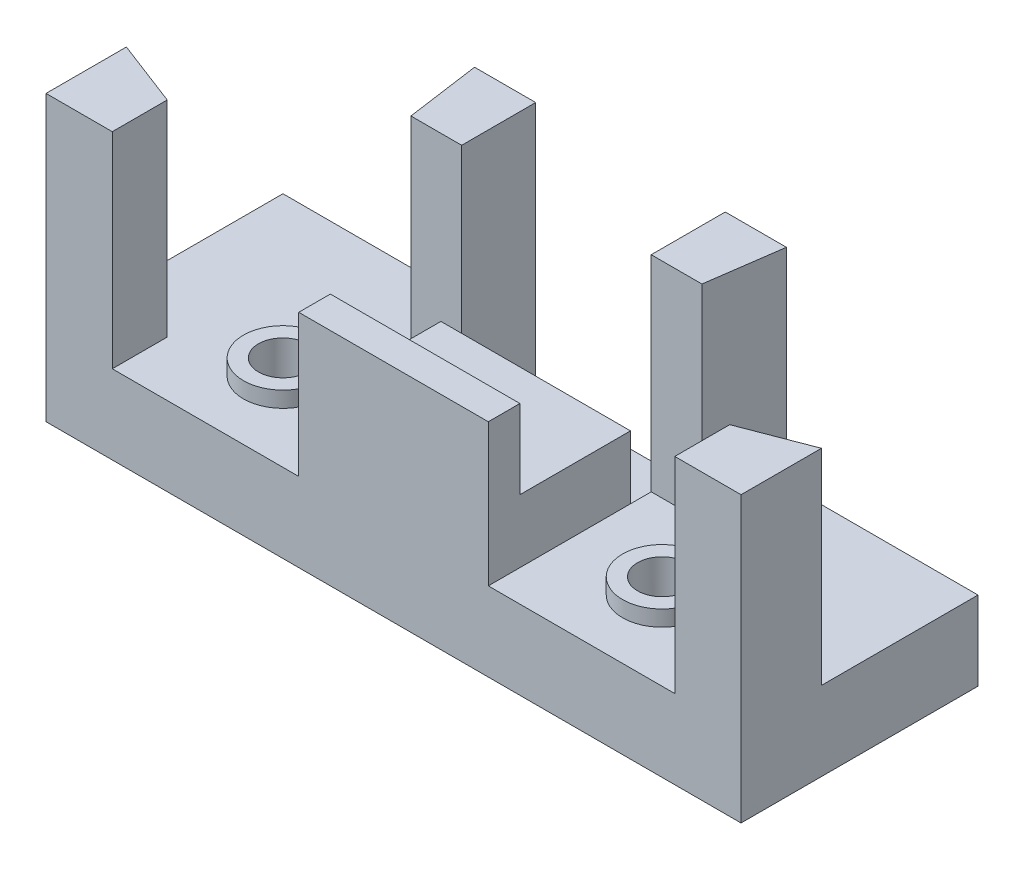
SolidWorks part; units mm, degrees
ref_plane "Front Plane" through (0, 0, 0) normal (0, 0, 1) x (1, 0, 0)
ref_plane "Top Plane" through (0, 0, 0) normal (0, 1, 0) x (1, 0, 0)
ref_plane "Right Plane" through (0, 0, 0) normal (1, 0, 0) x (0, 0, -1)
sketch "Sketch1" plane through (0, 0, 0) normal (0, 1, 0) x (1, 0, 0)
  line L1 (0, 0) -> (44, 0)
  line L2 (0, 0) -> (0, -15)
  line L3 (0, -15) -> (44, -15)
  line L4 (44, 0) -> (44, -15)
  dimension "D1" = 15
  dimension "D2" = 44
extrude "Boss-Extrude1" add sketch "Sketch1" along normal blind 5
sketch "Sketch2" plane through (0, 5, 0) normal (0, 1, 0) x (1, 0, 0)
  line L0 (44, 0) -> (0, 0) construction
  line L1 (16, 0) -> (28, 0)
  line L2 (16, 0) -> (16, -15)
  line L3 (16, -15) -> (28, -15)
  line L4 (28, 0) -> (28, -15)
  line L5 (0, -15) -> (44, -15) construction
  line L6 (22, 0) -> (22, -15) construction
  dimension "D1" = 6
  dimension "D2" = 6
extrude "Boss-Extrude2" add sketch "Sketch2" along normal blind 4
sketch "Sketch3" plane through (0, 5, 0) normal (0, 1, 0) x (1, 0, 0)
  line L0 (28, -15) -> (44, -15) construction
  line L4 (0, -15) -> (16, -15) construction
  line L5 (28, -15) -> (28, 0) construction
  line L6 (16, 0) -> (16, -15) construction
  circle A0 centre (10, -10) radius 1.55
  circle A1 centre (34, -10) radius 1.55
  dimension "D1" = 3.1
  dimension "D3" = 3.1
  dimension "D2" = 5
  dimension "D4" = 5
  dimension "D5" = 6
  dimension "D6" = 6
extrude "Cut-Extrude1" cut sketch "Sketch3" against normal blind 3
sketch "Sketch4" plane through (0, 9, 0) normal (0, 1, 0) x (1, 0, 0)
  line L1 (16, -15) -> (28, -15) construction
  line L2 (16, 0) -> (16, -15) construction
  circle A0 centre (22, -10) radius 1.55
  dimension "D1" = 3.1
  dimension "D2" = 5
  dimension "D3" = 6
extrude "Cut-Extrude2" cut sketch "Sketch4" against normal blind 3
sketch "Sketch5" plane through (0, 5, 0) normal (0, 1, 0) x (1, 0, 0)
  line L0 (22, 0) -> (22, -15) construction
  line L1 (28, 0) -> (16, 0) construction
  line L2 (16, -15) -> (28, -15) construction
  circle A0 centre (10, -10) radius 2.5
  circle A1 centre (10, -10) radius 1.55
  circle A2 centre (34, -10) radius 2.5
  circle A3 centre (34, -10) radius 1.55
  dimension "D1" = 5
extrude "Boss-Extrude3" add sketch "Sketch5" along normal blind 1
sketch "Sketch6" plane through (0, 9, 0) normal (0, 1, 0) x (1, 0, 0)
  line L0 (16, 0) -> (16, -15) construction
  line L1 (16, -13) -> (28, -13)
  line L2 (16, -13) -> (16, -15)
  line L3 (16, -15) -> (28, -15)
  line L4 (28, -13) -> (28, -15)
  dimension "D1" = 2
extrude "Boss-Extrude4" add sketch "Sketch6" along normal blind 5
sketch "Sketch8" plane through (0, 5, 0) normal (0, 1, 0) x (1, 0, 0)
  line L0 (34, -10) -> (44, -10) construction
  line L1 (44, -15) -> (44, 0) construction
  line L2 (34, -10) -> (44, -6.1614) construction
  line L3 (34, -10) -> (35.4054, 0) construction
  line L4 (44, 0) -> (28, 0) construction
  line L5 (34.7027, -5) -> (31.2368, -4.5129) construction
  line L6 (31.2368, -4.5129) -> (29.8332, -14.4994) construction
  line L7 (34, -10) -> (31.2123, -4.6869) construction
  line L8 (31.2123, -4.6869) -> (31.871, 0)
  line L11 (39, -8.0807) -> (40.2543, -11.3482) construction
  line L12 (40.2543, -11.3482) -> (30.7411, -15) construction
  line L13 (28, -15) -> (44, -15) construction
  line L14 (34, -10) -> (39.804, -11.5211) construction
  line L15 (39.804, -11.5211) -> (44, -9.9104)
  line L16 (22, 0) -> (22, -15) construction
  line L17 (28, 0) -> (16, 0) construction
  line L18 (16, -15) -> (28, -15) construction
  line L20 (28, 0) -> (31.871, 0)
  line L22 (44, -15) -> (44, -9.9104)
  line L24 (12.7877, -4.6869) -> (12.129, 0)
  line L25 (16, 0) -> (12.129, 0)
  line L27 (4.196, -11.5211) -> (0, -9.9104)
  line L28 (0, -15) -> (0, -9.9104)
  line L29 (31.2123, -4.6869) -> (28, -4.6869)
  line L30 (28, -13) -> (28, 0) construction
  line L31 (28, -4.6869) -> (28, 0)
  line L32 (39.804, -11.5211) -> (39.804, -15)
  line L33 (39.804, -15) -> (44, -15)
  line L34 (12.7877, -4.6869) -> (16, -4.6869)
  line L35 (16, -4.6869) -> (16, 0)
  line L36 (4.196, -11.5211) -> (4.196, -15)
  line L37 (4.196, -15) -> (0, -15)
  dimension "D1" = 21
  dimension "D2" = 82
  dimension "D3" = 3.5
  dimension "D4" = 90
  dimension "D5" = 6
  dimension "D6" = 90
  dimension "D7" = 3.5
  dimension "D8" = 6
  dimension "D9" = 90
extrude "Boss-Extrude5" add sketch "Sketch8" along normal blind 13
sketch "Sketch10" plane through (0, 9, 0) normal (0, 1, 0) x (1, 0, 0)
  line L0 (28, -13) -> (28, -4.6869) construction
  line L1 (16, 0) -> (28, 0)
  line L2 (16, 0) -> (16, -6)
  line L3 (16, -6) -> (28, -6)
  line L4 (28, 0) -> (28, -6)
  dimension "D1" = 6
extrude "Cut-Extrude4" cut sketch "Sketch10" against normal blind 7
